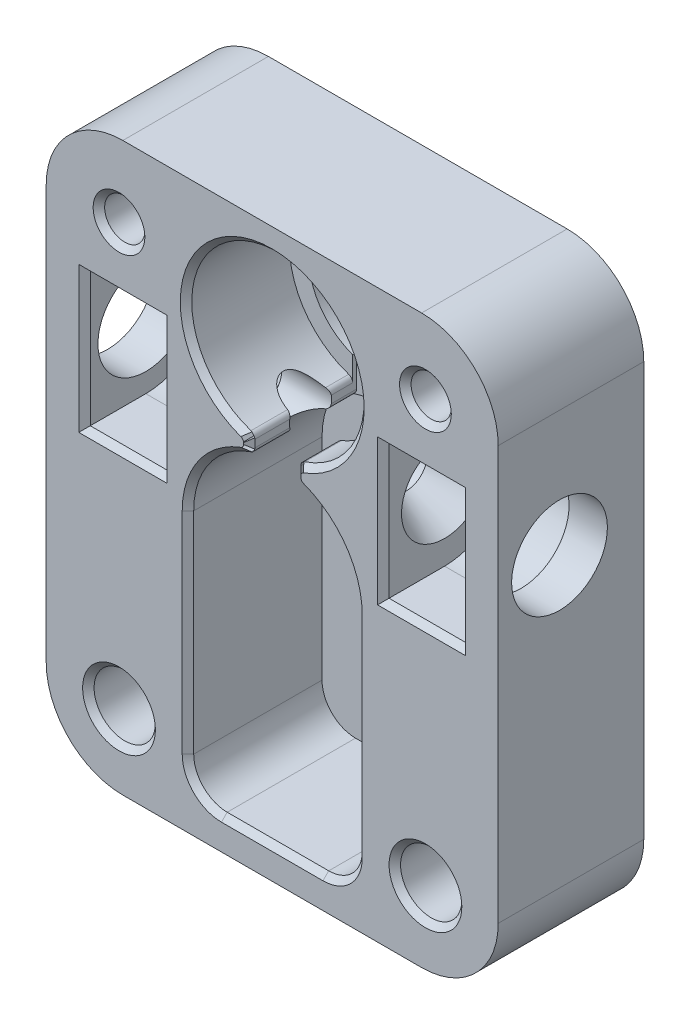
SolidWorks part; units mm, degrees
ref_plane "Front" through (0, 0, 0) normal (0, 0, 1) x (1, 0, 0)
ref_plane "Top" through (0, 0, 0) normal (0, 1, 0) x (1, 0, 0)
ref_plane "Right" through (0, 0, 0) normal (1, 0, 0) x (0, 0, -1)
sketch "Sketch1" plane through (0, 0, 0) normal (0, 0, 1) x (1, 0, 0)
  line L1 (11.8, 14.8) -> (-11.8, 14.8)
  line L2 (11.8, 14.8) -> (11.8, -14.8)
  line L3 (11.8, -14.8) -> (-11.8, -14.8)
  line L4 (-11.8, 14.8) -> (-11.8, -14.8)
  line L5 (11.8, 14.8) -> (-11.8, -14.8) construction
  line L6 (11.8, -14.8) -> (-11.8, 14.8) construction
  point P0 (0, 0)
  dimension "D1" = 23.6
  dimension "D2" = 29.6
extrude "Basic" add sketch "Sketch1" along normal blind 7.6
sketch "Sketch2" plane through (0, 0, 7.6) normal (0, 0, 1) x (1, 0, 0)
  circle A0 centre (0, 9) radius 3.5
  dimension "D1" = 7
  dimension "D2" = 9
extrude "Ø7.0 Hole (Rotating Magnet)" cut sketch "Sketch2" against normal through all
sketch "Sketch3" plane through (0, 0, 7.6) normal (0, 0, 1) x (1, 0, 0)
  circle A0 centre (0, 9) radius 4.5
  dimension "D1" = 9
extrude "Ø9.0 Hole (Rotating Magnet)" cut sketch "Sketch3" against normal blind 5.4
sketch "Sketch4" plane through (0, 0, 7.6) normal (0, 0, 1) x (1, 0, 0)
  line L0 (-11.8, -14.8) -> (11.8, -14.8) construction
  line L2 (-4.4, -0.4) -> (-4.4, -13.15)
  line L3 (-4.4, -13.15) -> (4.4, -13.15)
  line L4 (4.4, -0.4) -> (4.4, -13.15)
  arc A0 (-4.4, -0.4) -> (4.4, -0.4) centre (0, -0.4) cw
  circle A2 centre (0, 9) radius 3.5 construction
  point P4 (0, -13.15)
  point P9 (0, 4)
  dimension "D3" = 0.4
  dimension "D1" = 8.8
  dimension "D2" = 17.15
  dimension "D4" = 22.15
  dimension "D5" = 1.65
extrude "Thrust Bearing Chamber" cut sketch "Sketch4" against normal blind 7
fillet "R1.75: Thrust Bearing Chamber" radius 1.75 2 edges at (4.4, -13.15, 4.1) (-4.4, -13.15, 4.1)
sketch "Sketch5" plane through (0, 0, 7.6) normal (0, 0, 1) x (1, 0, 0)
  circle A0 centre (-8, 11) radius 1.05
  circle A1 centre (8, 11) radius 1.05
  circle A2 centre (-8, -11) radius 1.6
  circle A3 centre (8, -11) radius 1.6
  dimension "D5" = 2.1
  dimension "D6" = 3.2
  dimension "D1" = 8
  dimension "D2" = 8
  dimension "D3" = 11
  dimension "D4" = 11
extrude "Mounting holes  Ø2.1 & Ø3.2" cut sketch "Sketch5" against normal through all
sketch "Position Plane Filament Transit" plane through (0, 0, 7.6) normal (0, 0, 1) x (1, 0, 0)
  line L1 (0, 4) -> (0, 4.5) construction
  line L2 (-11.8, 4.25) -> (11.8, 4.25) construction
  line L3 (-11.8, 14.8) -> (-11.8, -14.8) construction
  arc A0 (4.4, -0.4) -> (-4.4, -0.4) centre (0, -0.4) ccw construction
  circle A1 centre (0, 9) radius 4.5 construction
  point P12 (0, 4.25)
  point P13 (0, 4.25)
ref_plane "Plane: Filament Transit" through (0, 4.25, 0) normal (0, -1, 0) x (1, 0, 0)
sketch "Sketch8" plane through (0, 4.25, 0) normal (0, -1, 0) x (1, 0, 0)
  line L0 (-15, 4.4) -> (15, 4.4) construction
  line L1 (-11.8, 7.6) -> (-11.8, 0) construction
  line L3 (-11.8, 6.9) -> (-9.8, 6.9)
  line L4 (-9.8, 6.9) -> (-9.8, 7.9)
  line L5 (-9.8, 7.9) -> (-5.8, 7.9)
  line L7 (-5.8, 7.9) -> (-5.8, 6.65)
  line L8 (-5.8, 6.65) -> (-3.8, 6.65)
  line L9 (-3.8, 6.65) -> (-3.8, 5.5)
  line L10 (-3.8, 5.5) -> (3.8, 5.5)
  line L11 (11.8, 7.6) -> (11.8, 0) construction
  line L12 (3.8, 5.5) -> (3.8, 6.65)
  line L13 (3.8, 6.65) -> (5.8, 6.65)
  line L14 (5.8, 6.65) -> (5.8, 7.9)
  line L15 (5.8, 7.9) -> (9.8, 7.9)
  line L16 (9.8, 7.9) -> (9.8, 6.9)
  line L17 (9.8, 6.9) -> (11.8, 6.9)
  line L18 (-11.8, 6.9) -> (-11.8, 4.4)
  line L19 (-11.8, 4.4) -> (11.8, 4.4)
  line L20 (11.8, 4.4) -> (11.8, 6.9)
  point P5 (0, 5.5)
  point P26 (0, 4.4)
  dimension "D1" = 5
  dimension "D2" = 7
  dimension "D3" = 4.4
  dimension "D4" = 4.5
  dimension "D5" = 2
  dimension "D6" = 4
  dimension "D7" = 2
  dimension "D8" = 2.2
  dimension "D9" = 30
  dimension "D10" = 6
revolve "Filament Transit 1" cut sketch "Sketch8" angle 360 about L0
sketch "Sketch12" plane through (0, 4.25, 0) normal (0, -1, 0) x (1, 0, 0)
  line L0 (5.8, 6.65) -> (3.8, 5.5)
  line L1 (3.8, 5.5) -> (3.8, 6.65)
  line L2 (3.8, 6.65) -> (5.8, 6.65)
  line L3 (-15, 4.4) -> (15, 4.4) construction
  line L4 (-15, 4.4) -> (15, 4.4) construction
  line L5 (-5.8, 6.65) -> (-3.8, 5.5)
  line L6 (-3.8, 6.65) -> (-3.8, 5.5) construction
  line L7 (-3.8, 5.5) -> (-3.8, 6.65)
  line L8 (-3.8, 6.65) -> (-5.8, 6.65)
  dimension "D1" = 29.899
revolve "Filament Transit 2" add sketch "Sketch12" angle 360 about L4
sketch "Sketch15" plane through (5.8, 0, 0) normal (1, 0, 0) x (0, 0, -1)
  line L0 (-4.4, 0.75) -> (-7.6, 0.75)
  line L1 (-7.6, 5.6677) -> (-7.6, 2.8323)
  line L3 (-7.6, -14.8) -> (-7.6, 14.8) construction
  line L4 (-4.4, 7.75) -> (-7.6, 7.75)
  line L5 (-7.6, 7.75) -> (-7.6, 0.75)
  arc A1 (-7.6, 2.8323) -> (-7.6, 5.6677) centre (-4.4, 4.25) ccw
  arc A2 (-4.4, 0.75) -> (-4.4, 7.75) centre (-4.4, 4.25) ccw
  dimension "D1" = 0
extrude "Filament Transit 3.1" cut sketch "Sketch15" along normal up to surface (4 mm away) up to face at (9.8, 1.75, 4.4)
sketch "Sketch16" plane through (-5.8, 0, 0) normal (-1, 0, 0) x (0, 0, 1)
  line L3 (4.4, 0.75) -> (7.6, 0.75)
  line L4 (7.6, 0.75) -> (7.6, 7.75)
  line L5 (7.6, 7.75) -> (4.4, 7.75)
  line L6 (4.4, 0.75) -> (7.6, 0.75)
  line L7 (7.6, 0.75) -> (7.6, 7.75)
  line L8 (7.6, 7.75) -> (4.4, 7.75)
  arc A1 (4.4, 7.75) -> (4.4, 0.75) centre (4.4, 4.25) ccw
  arc A2 (4.4, 7.75) -> (4.4, 0.75) centre (4.4, 4.25) ccw
  dimension "D1" = 0
extrude "Filament Transit 3.2" cut sketch "Sketch16" along normal up to surface (4 mm away) up to face at (-9.8, 1.75, 4.4)
sketch "Sketch9" plane through (0, 0, 7.6) normal (0, 0, 1) x (1, 0, 0)
  line L2 (-1.2, 5.7121) -> (-1.2, 0)
  line L3 (-1.2, 0) -> (1.2, 0)
  line L4 (1.2, 5.7121) -> (1.2, 0)
  circle A0 centre (0, 9) radius 3.5 construction
  arc A1 (-1.2, 5.7121) -> (1.2, 5.7121) centre (0, 9) ccw
  dimension "D1" = 2.4
extrude "Bearing Release: Thrust Bearing Chamber " cut sketch "Sketch9" against normal blind 5.6
sketch "Sketch10" plane through (0, 0, 7.6) normal (0, 0, 1) x (1, 0, 0)
  circle A0 centre (-8, 0) radius 1.5
  circle A1 centre (8, 0) radius 1.5
  dimension "D1" = 3
  dimension "D2" = 8
  dimension "D3" = 8
extrude "Ø3.0 Nipples" [suppressed] add sketch "Sketch10" along normal blind 1
fillet "R0.3: Nipples" [suppressed] radius 0.3
fillet "R4: Basic" radius 4 4 edges at (11.8, -14.8, 3.8) (-11.8, -14.8, 3.8) (-11.8, 14.8, 3.8) (11.8, 14.8, 3.8)
chamfer "0.3×45°" distance 0.3 angle 45 22 edges at (3.51, 2.2533, 7.6) (4.4, -5.9, 7.6) (3.8874, -12.6374, 7.6) (0, -13.15, 7.6) (-3.8874, -12.6374, 7.6) (-4.4, -5.9, 7.6) (-3.51, 2.2533, 7.6) (-1.2, 4.2481, 7.6) (1.2, 4.2481, 7.6) (0, 13.5, 7.6) (9.6, -11, 7.6) (-6.4, -11, 7.6) (-5.8, 4.25, 7.6) (-9.8, 4.25, 7.6) (-6.95, 11, 7.6) (9.05, 11, 7.6) (5.8, 4.25, 7.6) (9.8, 4.25, 7.6) (-7.8, 0.75, 7.6) (-7.8, 7.75, 7.6) (7.8, 0.75, 7.6) (7.8, 7.75, 7.6)
fillet "R0.3" radius 0.3 12 edges at (1.2, 3.8332, 6.359) (1.2, 4.663, 6.3598) (1.2, 4.663, 2.7902) (1.2, 3.8332, 2.691) (-1.2, 4.663, 2.7902) (-1.2, 3.8332, 2.691) (-1.2, 3.8332, 6.359) (-1.2, 4.663, 6.3598)
